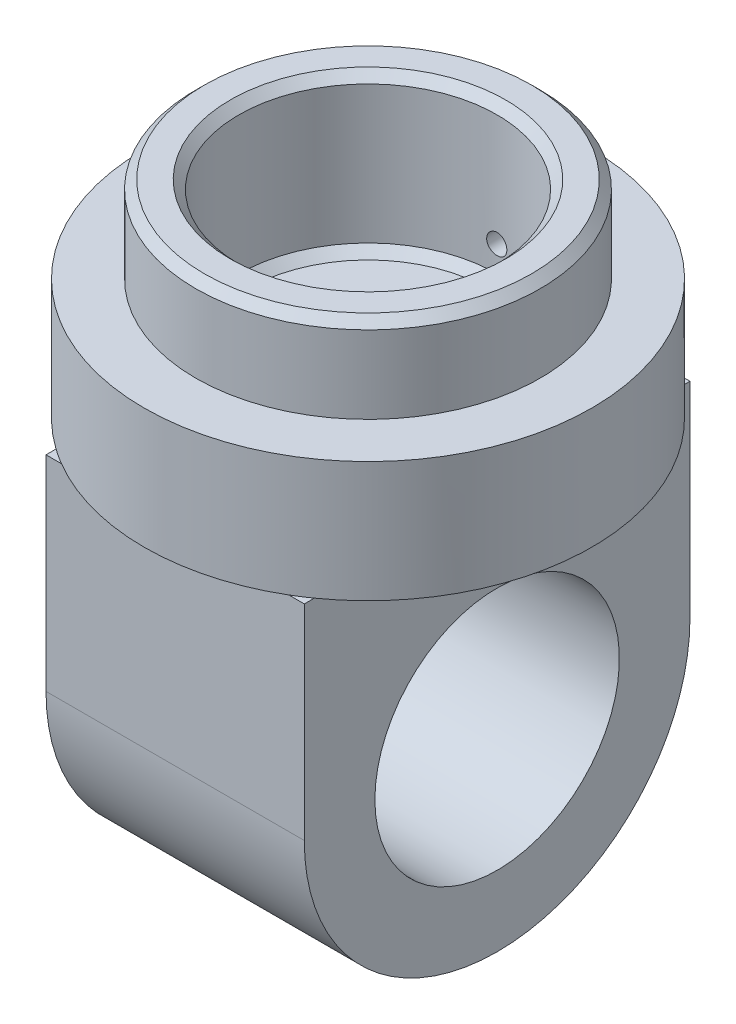
SolidWorks part; units mm, degrees
ref_plane "Front Plane" through (0, 0, 0) normal (0, 0, 1) x (1, 0, 0)
ref_plane "Top Plane" through (0, 0, 0) normal (0, 1, 0) x (1, 0, 0)
ref_plane "Right Plane" through (0, 0, 0) normal (1, 0, 0) x (0, 0, -1)
sketch "Sketch1" plane through (0, 0, 0) normal (0, 1, 0) x (1, 0, 0)
  circle A0 centre (0, 0) radius 13
  dimension "D1" = 26
extrude "Boss-Extrude1" add sketch "Sketch1" along normal blind 7
sketch "Sketch2" plane through (0, 7, 0) normal (0, 1, 0) x (1, 0, 0)
  circle A0 centre (0, 0) radius 10
  dimension "D1" = 20
extrude "Boss-Extrude2" add sketch "Sketch2" along normal blind 5
sketch "Sketch3" plane through (0, 12, 0) normal (0, 1, 0) x (1, 0, 0)
  circle A0 centre (0, 0) radius 7.5
  dimension "D1" = 15
extrude "Cut-Extrude1" cut sketch "Sketch3" against normal blind 9
chamfer "Chamfer1" distance 0.5 angle 45 3 edges at (0, 12, 10) (0, 3, 7.5) (0, 12, 7.5)
sketch "Sketch4" plane through (0, 0, 0) normal (0, 0, 1) x (1, 0, 0)
  circle A0 centre (0, 5) radius 0.585
  dimension "D1" = 1.17
  dimension "D2" = 5
extrude "Cut-Extrude2" cut sketch "Sketch4" against normal through all
sketch "Sketch5" plane through (0, 0, 0) normal (0, -1, 0) x (1, 0, 0)
  line L1 (-7.5, -11.2) -> (7.5, -11.2)
  line L2 (-7.5, -11.2) -> (-7.5, 11.2)
  line L3 (-7.5, 11.2) -> (7.5, 11.2)
  line L4 (7.5, -11.2) -> (7.5, 11.2)
  line L5 (-7.5, -11.2) -> (7.5, 11.2) construction
  line L6 (-7.5, 11.2) -> (7.5, -11.2) construction
  point P0 (0, 0)
  dimension "D1" = 15
  dimension "D2" = 22.4
extrude "Boss-Extrude3" add sketch "Sketch5" along normal blind 23.1
fillet "Fillet1" radius 11.2 2 edges at (0, -23.1, 11.2) (0, -23.1, -11.2)
sketch "Sketch8" plane through (-7.5, 0, 0) normal (-1, 0, 0) x (0, 0, 1)
  circle A0 centre (0, -11.9) radius 7.1
  dimension "D1" = 14.2
  dimension "D2" = 11.9
extrude "Cut-Extrude4" cut sketch "Sketch8" against normal up to surface (15 mm away) up to face at (7.5, -7.3627, 0)
ref_plane "Plane1" through (0, 0, -13) normal (0, 0, -1) x (-1, 0, 0)
sketch "Sketch9" plane through (0, 0, -13) normal (0, 0, -1) x (-1, 0, 0)
  circle A0 centre (0, 5) radius 1.17
  dimension "D1" = 2.34
extrude "Cut-Extrude5" cut sketch "Sketch9" against normal blind 1
equation "\"pin_bore\"=14.20"
equation "\"top_outer_diameter\"=22.40"
equation "\"D1@Sketch8\"=\"pin_bore\""
equation "\"D1@Boss-Extrude3\"=\"bottom_height\""
equation "\"bottom_height\"=23.10"
equation "\"D2@Sketch5\"=\"top_outer_diameter\""
equation "\"D1@Fillet1\"=\"top_outer_diameter\"/2"
equation "\"bottom_bore_height\"=11.90"
equation "\"D2@Sketch8\"=\"bottom_bore_height\""
equation "\"valve_diameter\"=1.17"
equation "\"D1@Sketch4\"=\"valve_diameter\""
equation "\"D1@Sketch9\"=\"valve_diameter\"*2"
